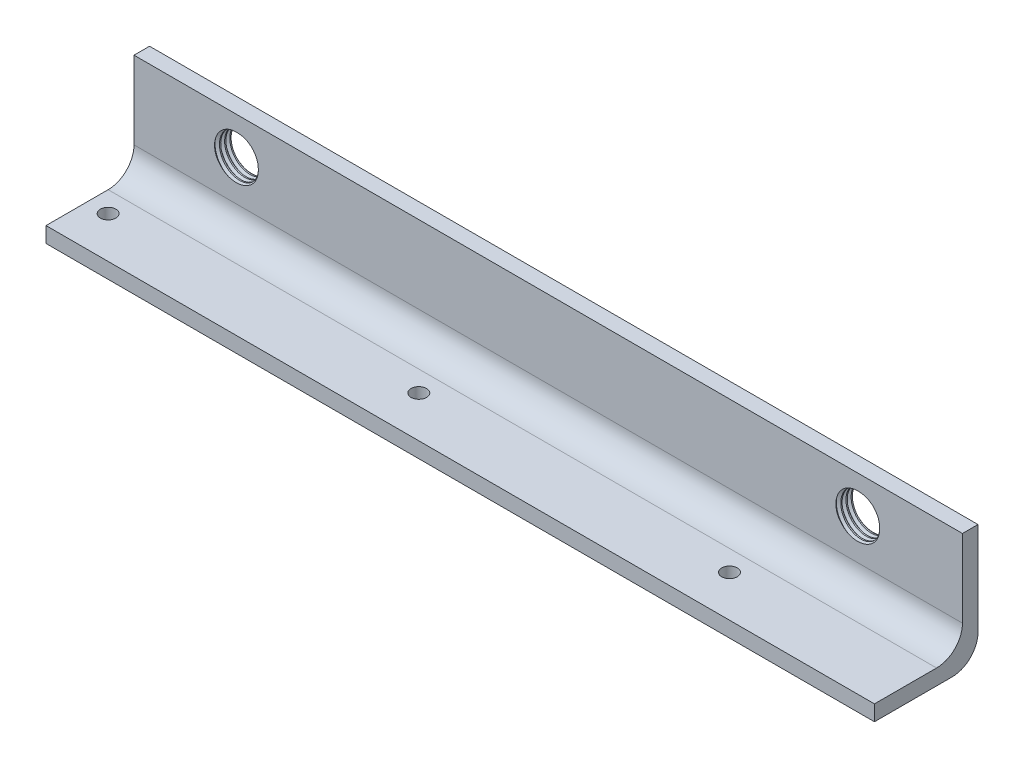
SolidWorks part; units mm, degrees
ref_plane "Front Plane" through (0, 0, 0) normal (0, 0, 1) x (1, 0, 0)
ref_plane "Top Plane" through (0, 0, 0) normal (0, 1, 0) x (1, 0, 0)
ref_plane "Right Plane" through (0, 0, 0) normal (1, 0, 0) x (0, 0, -1)
sketch "Sketch1" plane through (0, 0, 0) normal (0, 1, 0) x (1, 0, 0)
  line L1 (-80, -10) -> (80, -10)
  line L2 (-80, -10) -> (-80, 10)
  line L3 (-80, 10) -> (80, 10)
  line L4 (80, -10) -> (80, 10)
  line L5 (-80, -10) -> (80, 10) construction
  line L6 (-80, 10) -> (80, -10) construction
  point P0 (0, 0)
  dimension "D1" = 20
  dimension "D2" = 160
extrude "Boss-Extrude1" add sketch "Sketch1" along normal blind 3
sketch "Sketch2" plane through (0, 3, 0) normal (0, 1, 0) x (1, 0, 0)
  line L0 (80, -10) -> (80, 10) construction
  line L1 (-80, 10) -> (80, 10)
  line L2 (-80, 10) -> (-80, 7)
  line L3 (-80, 7) -> (80, 7)
  line L4 (80, 10) -> (80, 7)
  dimension "D1" = 3
extrude "Boss-Extrude2" add sketch "Sketch2" along normal blind 20
fillet "Fillet1" radius 5 1 edges at (0, 3, -7)
sketch "Sketch3" plane through (0, 3, 0) normal (0, 1, 0) x (1, 0, 0)
  line L0 (-80, 2) -> (-80, -10) construction
  line L1 (80, 2) -> (-80, 2) construction
  circle A0 centre (-76, -2) radius 1.5
  circle A1 centre (-16, -2) radius 1.5
  circle A2 centre (44, -2) radius 1.5
  dimension "D1" = 3
  dimension "D2" = 4
  dimension "D4" = 4
  dimension "D5" = 60
  dimension "D3" = 3
extrude "Cut-Extrude1" cut sketch "Sketch3" against normal through all
sketch "Sketch4" plane through (0, 0, -10) normal (0, 0, -1) x (-1, 0, 0)
  line L0 (-80, 23) -> (-80, 0) construction
  line L1 (-80, 23) -> (80, 23) construction
  line L2 (0, 0) -> (0, 10.2486) construction
  line L3 (-80, 0) -> (80, 0) construction
  line L5 (80, 23) -> (80, 0) construction
  circle A0 centre (-60, 16) radius 4
  circle A1 centre (60, 16) radius 4
  dimension "D1" = 8
  dimension "D6" = 8
  dimension "D2" = 20
  dimension "D3" = 7
  dimension "D4" = 20
  dimension "D5" = 7
extrude "Cut-Extrude2" cut sketch "Sketch4" against normal up to next
thread "Thread1" pitch 1 method cut profile "Thread Profile1" start angle 0, offset 1, length 0, pitch 1, diameter 8
ref_plane "Plane1" through (64, 16, -11) normal (0, -1, 0) x (1, 0, 0)
sketch "Thread Profile1" plane through (64, 16, -11) normal (0, -1, 0) x (1, 0, 0)
  line L0 (0, 0) -> (0, 1) construction
  line L1 (0, 0) -> (0.5413, 0.3125)
  line L2 (0.5413, 0.3125) -> (0.5413, 0.4375)
  line L3 (0.5413, 0.4375) -> (0, 0.75)
  line L4 (0.5413, 0.375) -> (0, 0.375) construction
  line L11 (0, 0) -> (0, 0.75)
  point P2 (0, 0)
  dimension "Pitch" = 1
  dimension "Profile_Angle" = 60
  dimension "Profile_Land" = 0.125
  dimension "Profile_Height" = 0.5413
thread "Thread2" pitch 1 method cut profile "Thread Profile2" start angle 0, offset 1, length 0, pitch 1, diameter 8
ref_plane "Plane2" through (-56, 16, -11) normal (0, -1, 0) x (1, 0, 0)
sketch "Thread Profile2" plane through (-56, 16, -11) normal (0, -1, 0) x (1, 0, 0)
  line L0 (0, 0) -> (0, 1) construction
  line L1 (0, 0) -> (0.5413, 0.3125)
  line L2 (0.5413, 0.3125) -> (0.5413, 0.4375)
  line L3 (0.5413, 0.4375) -> (0, 0.75)
  line L4 (0.5413, 0.375) -> (0, 0.375) construction
  line L11 (0, 0) -> (0, 0.75)
  point P2 (0, 0)
  dimension "Pitch" = 1
  dimension "Profile_Angle" = 60
  dimension "Profile_Land" = 0.125
  dimension "Profile_Height" = 0.5413
fillet "Fillet2" radius 5 1 edges at (0, 0, -10)
